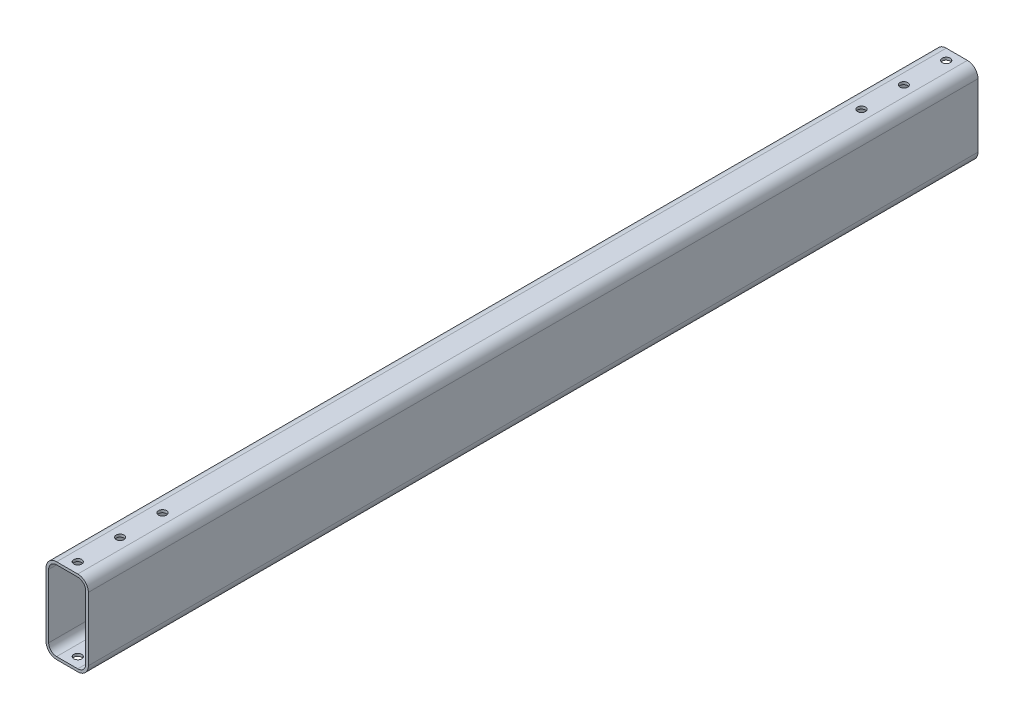
SolidWorks part; units mm, degrees
material "6061-T6 (SS)"
ref_plane "Front Plane" through (0, 0, 0) normal (0, 0, 1) x (1, 0, 0)
ref_plane "Top Plane" through (0, 0, 0) normal (0, 1, 0) x (1, 0, 0)
ref_plane "Right Plane" through (0, 0, 0) normal (1, 0, 0) x (0, 0, -1)
sketch "Sketch1" plane through (0, 0, 0) normal (0, 0, 1) x (1, 0, 0)
  line L1 (-6.35, -25.4) -> (6.35, -25.4)
  line L2 (-12.7, -19.05) -> (-12.7, 19.05)
  line L3 (-6.35, 25.4) -> (6.35, 25.4)
  line L4 (12.7, -19.05) -> (12.7, 19.05)
  line L5 (-12.7, -25.4) -> (12.7, 25.4) construction
  line L6 (-12.7, 25.4) -> (12.7, -25.4) construction
  arc A0 (-12.7, -19.05) -> (-6.35, -25.4) centre (-6.35, -19.05) ccw
  arc A1 (6.35, -25.4) -> (12.7, -19.05) centre (6.35, -19.05) ccw
  arc A2 (6.35, 25.4) -> (12.7, 19.05) centre (6.35, 19.05) cw
  arc A3 (-12.7, 19.05) -> (-6.35, 25.4) centre (-6.35, 19.05) cw
  point P0 (0, 0)
  dimension "D3" = 6.35
  dimension "D1" = 50.8
  dimension "D2" = 25.4
extrude "Extrude-Thin1" add sketch "Sketch1" along normal blind 533.4 thin thin type one direction reverse wall 1.5875
hole_wizard "3/16 (0.1875) Diameter Hole1" positions "3DSketch1" profile "Sketch3" hole size "3/16" standard "ANSI Inch" end condition through all
sketch3d "3DSketch1"
  line L1 (6.35, 25.4, 0) -> (-6.35, 25.4, 0) construction
  line L6 (0, 25.4, 533.4) -> (0, 25.4, 0) construction
  line L7 (6.35, 25.4, 533.4) -> (-6.35, 25.4, 533.4) construction
  point P57 (0, 25.4, 6.35)
  point P59 (0, 25.4, 31.75)
  point P61 (0, 25.4, 57.15)
  point P63 (0, 25.4, 501.65)
  point P65 (0, 25.4, 476.25)
  point P67 (0, 25.4, 527.05)
  dimension "D1" = 25.4
  dimension "D2" = 25.4
  dimension "D3" = 6.35
  dimension "D4" = 25.4
  dimension "D5" = 25.4
  dimension "D6" = 6.35
sketch "Sketch3" plane through (0, 25.4, 527.05) normal (1, 0, 0) x (0, 0, 1)
  line L0 (0, 0) -> (0, 50.8)
  line L1 (0, 50.8) -> (2.3812, 50.8)
  line L2 (2.3812, 50.8) -> (2.3812, 0)
  line L5 (2.3812, 0) -> (0, 0)
  line L11 (0, -6.35) -> (0, 107.95) construction
  dimension "Thru Hole Dia." = 4.7625
  dimension "Thru Hole Depth" = 50.8
hole_wizard "3/16 (0.195) Diameter Hole1" positions "Sketch4" profile "Sketch5" hole size "3/16" standard "ANSI Inch" end condition up to next
sketch "Sketch4" plane through (0, -25.4, 0) normal (0, -1, 0) x (-1, 0, 0)
  point P3 (3.175, -121.1947)
  point P6 (-3.175, -146.5947)
  point P9 (3.175, -171.9947)
  point P12 (-3.175, -197.3947)
  point P15 (-3.175, -349.7947)
  point P18 (3.175, -375.1947)
  point P21 (-3.175, -400.5947)
  point P24 (3.175, -425.9947)
  point P29 (0, 0)
sketch "Sketch5" plane through (-3.175, -25.4, 121.1947) normal (1, 0, 0) x (0, 0, -1)
  line L0 (0, 0) -> (0, 1.5875)
  line L1 (0, 1.5875) -> (2.4765, 1.5875)
  line L2 (2.4765, 1.5875) -> (2.4765, 0)
  line L5 (2.4765, 0) -> (0, 0)
  line L11 (0, -6.35) -> (0, 107.95) construction
  dimension "Thru Hole Dia." = 4.953
  dimension "Thru Hole Depth" = 1.5875
